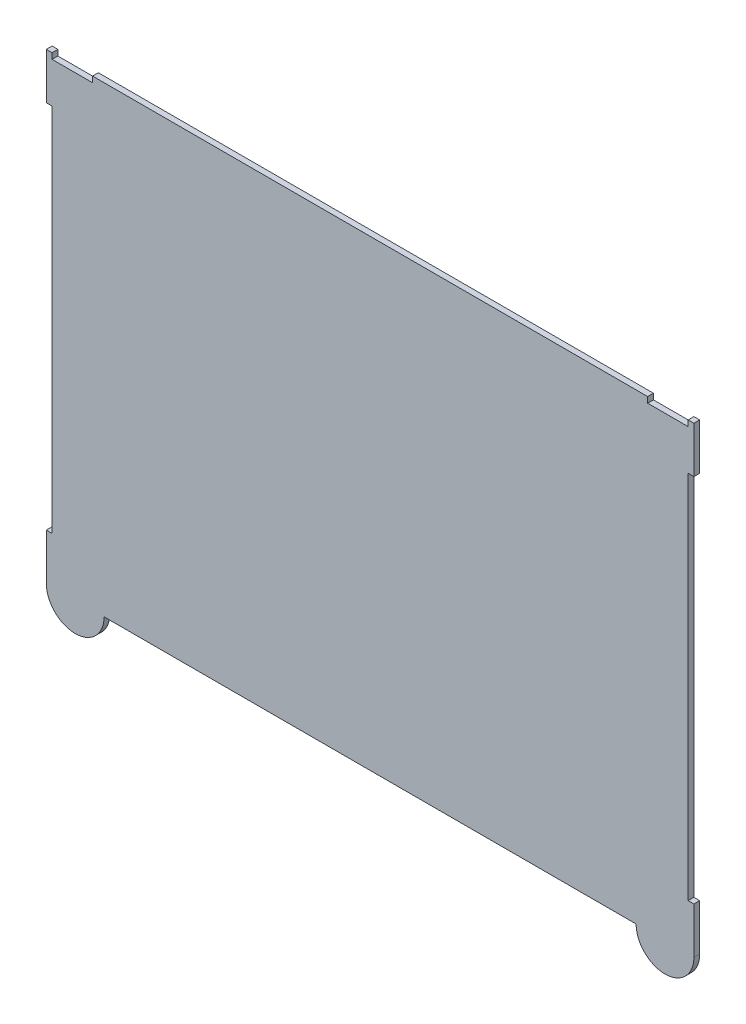
SolidWorks part; units mm, degrees
ref_plane "Front Plane" through (0, 0, 0) normal (0, 0, 1) x (1, 0, 0)
ref_plane "Top Plane" through (0, 0, 0) normal (0, 1, 0) x (1, 0, 0)
ref_plane "Right Plane" through (0, 0, 0) normal (1, 0, 0) x (0, 0, -1)
sketch "Sketch1" plane through (0, 0, 0) normal (0, 0, 1) x (1, 0, 0)
  line L0 (0, 228.6) -> (0, 250.825)
  line L1 (31.75, 0) -> (323.85, 0)
  line L2 (0, 0) -> (0, 25.4)
  line L3 (3.175, 250.825) -> (25.4, 250.825)
  line L4 (355.6, 0) -> (355.6, 25.4)
  line L5 (0, 228.6) -> (3.175, 228.6)
  line L7 (0, 25.4) -> (3.175, 25.4)
  line L8 (3.175, 228.6) -> (3.175, 25.4)
  line L9 (355.6, 228.6) -> (352.425, 228.6)
  line L11 (355.6, 25.4) -> (352.425, 25.4)
  line L12 (352.425, 228.6) -> (352.425, 25.4)
  line L17 (355.6, 228.6) -> (355.6, 250.825)
  line L18 (330.2, 250.825) -> (352.425, 250.825)
  line L19 (0, 250.825) -> (0, 254)
  line L20 (0, 254) -> (3.175, 254)
  line L21 (25.4, 250.825) -> (25.4, 254)
  line L22 (25.4, 254) -> (330.2, 254)
  line L23 (330.2, 254) -> (330.2, 250.825)
  line L24 (3.175, 254) -> (3.175, 250.825)
  line L25 (355.6, 250.825) -> (355.6, 254)
  line L26 (355.6, 254) -> (352.425, 254)
  line L27 (352.425, 254) -> (352.425, 250.825)
  arc A0 (0, 0) -> (31.75, 0) centre (15.875, 0) ccw
  arc A1 (355.6, 0) -> (323.85, 0) centre (339.725, 0) cw
  dimension "D12" = 15.875
  dimension "D1" = 250.825
  dimension "D2" = 355.6
  dimension "D4" = 3.175
  dimension "D5" = 3.175
  dimension "D6" = 203.2
  dimension "D8" = 203.2
  dimension "D9" = 25.4
  dimension "D10" = 25.4
  dimension "D13" = 3.175
extrude "Boss-Extrude1" add sketch "Sketch1" along normal blind 3.175
